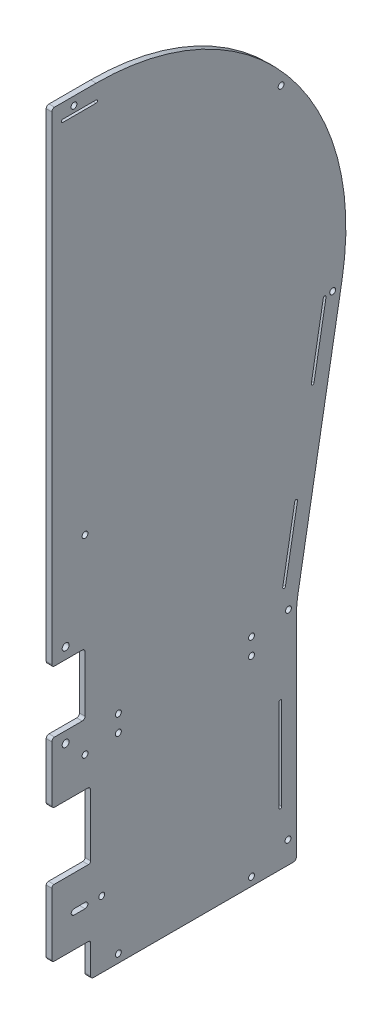
SolidWorks part; units mm, degrees
material "PC High Viscosity"
ref_plane "Front Plane" through (0, 0, 0) normal (0, 0, 1) x (1, 0, 0)
ref_plane "Top Plane" through (0, 0, 0) normal (0, 1, 0) x (1, 0, 0)
ref_plane "Right Plane" through (0, 0, 0) normal (1, 0, 0) x (0, 0, -1)
sketch "Sketch1" plane through (0, 0, 0) normal (1, 0, 0) x (0, 0, -1)
  line L0 (0, 0) -> (50.8, 0) construction
  line L1 (313.4482, -313.012) -> (263.1137, -598.4731) construction
  line L2 (260.7743, -625.2127) -> (260.7743, -865.7507) construction
  line L3 (0, 19.05) -> (50.8, 19.05)
  line L4 (332.2088, -316.32) -> (281.8743, -601.7811)
  line L5 (279.8243, -625.2127) -> (279.8243, -865.7507)
  line L6 (0, 19.05) -> (0, -534.7716)
  line L7 (0, -534.7716) -> (38.1, -534.7716)
  line L8 (38.1, -534.7716) -> (38.1, -605.1296)
  line L9 (38.1, -605.1296) -> (0, -605.1296)
  line L10 (0, -605.1296) -> (0, -674.7002)
  line L11 (0, -674.7002) -> (44.45, -674.7002)
  line L12 (44.45, -674.7002) -> (44.45, -865.7507)
  line L13 (44.45, -865.7507) -> (279.8243, -865.7507)
  line L14 (0, 1.5875) -> (50.8, 1.5875) construction
  line L15 (315.0116, -313.2876) -> (264.6771, -598.7487) construction
  line L16 (262.3618, -625.2127) -> (262.3618, -865.7507) construction
  arc A0 (50.8, 0) -> (313.4482, -313.012) centre (50.8, -266.7) cw construction
  arc A1 (263.1137, -598.4731) -> (260.7743, -625.2127) centre (414.7618, -625.2127) ccw construction
  arc A2 (50.8, 19.05) -> (332.2088, -316.32) centre (50.8, -266.7) cw
  arc A3 (281.8743, -601.7811) -> (279.8243, -625.2127) centre (414.7618, -625.2127) ccw
  arc A4 (50.8, 1.5875) -> (315.0116, -313.2876) centre (50.8, -266.7) cw construction
  arc A5 (264.6771, -598.7487) -> (262.3618, -625.2127) centre (414.7618, -625.2127) ccw construction
  point P23 (0, -333.375)
  point P25 (0, -3.175)
  point P27 (0, -681.0502)
  point P28 (0, -535.1526)
  dimension "D1" = 266.7
  dimension "D2" = 153.9875
  dimension "D3" = 80
  dimension "D4" = 50.8
  dimension "D5" = 240.538
  dimension "D6" = 289.8648
  dimension "D8" = 3.175
  dimension "D9" = 330.2
  dimension "D10" = 70.358
  dimension "D11" = 38.1
  dimension "D12" = 201.7776
  dimension "D13" = 0.381
  dimension "D14" = 347.6752
  dimension "D15" = 6.35
  dimension "D16" = 44.45
  dimension "D18" = 216.3243
  dimension "D7" = 19.05
  dimension "D17" = 1.5875
extrude "Boss-Extrude1" add sketch "Sketch1" along normal blind 6.35
hole_wizard "1/4 Clearance Hole1" positions "Sketch2" profile "Sketch3" hole size "1/4" standard "ANSI Inch" end condition through all
sketch "Sketch2" plane through (6.35, 0, 0) normal (1, 0, 0) x (0, 0, -1)
  line L0 (0, 1.5875) -> (50.8, 1.5875) construction
  line L1 (0, 19.05) -> (0, -534.7716) construction
  line L2 (256.3201, -94.2481) -> (262.4006, -89.146) construction
  line L6 (256.3201, -94.2481) -> (278.7716, -121.0047) construction
  line L8 (315.0116, -313.2876) -> (264.6771, -598.7487) construction
  line L9 (313.4482, -313.012) -> (315.0116, -313.2876) construction
  line L11 (262.9417, -611.9302) -> (270.849, -612.622) construction
  line L13 (262.9417, -611.9302) -> (264.7529, -591.2286) construction
  line L15 (262.3618, -625.2127) -> (262.3618, -865.7507) construction
  line L16 (44.45, -865.7507) -> (279.8243, -865.7507) construction
  line L17 (0, -605.1296) -> (0, -674.7002) construction
  line L18 (38.1, -569.9506) -> (0, -569.9506) construction
  line L19 (38.1, -534.7716) -> (38.1, -605.1296) construction
  line L23 (0, 19.05) -> (0, -534.7716) construction
  line L25 (44.45, -674.7002) -> (44.45, -865.7507) construction
  line L26 (44.45, -865.7507) -> (279.8243, -865.7507) construction
  line L27 (44.45, -627.9051) -> (279.8243, -627.9051) construction
  line L28 (279.8243, -865.7507) -> (279.8243, -625.2127) construction
  arc A0 (315.0116, -313.2876) -> (50.8, 1.5875) centre (50.8, -266.7) ccw construction
  arc A1 (264.6771, -598.7487) -> (262.3618, -625.2127) centre (414.7618, -625.2127) ccw construction
  point P0 (25.4, 9.525)
  point P2 (262.4006, -89.146)
  point P4 (321.4502, -322.4829)
  point P6 (270.849, -612.622)
  point P8 (270.2993, -840.3507)
  point P10 (38.1, -639.9149)
  point P12 (38.1, -422.275)
  point P68 (0, -639.9149)
  point P97 (76.2, -637.4301)
  point P99 (228.6, -637.4301)
  point P101 (76.2, -856.2257)
  point P103 (228.6, -856.2257)
  point P122 (228.6, -618.3801)
  point P123 (76.2, -618.3801)
  point P126 (57.15, -789.5507)
  point P127 (186.2677, -856.2257)
  dimension "D1" = 7.9375
  dimension "D2" = 25.4
  dimension "D3" = 7.9375
  dimension "D4" = 7.9375
  dimension "D5" = 7.9375
  dimension "D6" = 7.9375
  dimension "D7" = 7.9375
  dimension "D8" = 25.4
  dimension "D9" = 38.1
  dimension "D10" = 38.1
  dimension "D11" = 88.9
  dimension "D12" = 76.2
  dimension "D13" = 12.7
  dimension "D14" = 152.4
  dimension "D15" = 31.75
  dimension "D16" = 9.525
  dimension "D17" = 237.8456
  dimension "D18" = 9.525
sketch "Sketch3" plane through (6.35, 9.525, -25.4) normal (0, 1, 0) x (0, 0, -1)
  line L0 (0, 0) -> (0, 6.35)
  line L1 (0, 6.35) -> (3.3782, 6.35)
  line L2 (3.3782, 6.35) -> (3.3782, 0)
  line L5 (3.3782, 0) -> (0, 0)
  line L11 (0, -6.35) -> (0, 107.95) construction
  dimension "Thru Hole Dia." = 6.7564
  dimension "Thru Hole Depth" = 6.35
sketch "Sketch4" plane through (6.35, 0, 0) normal (1, 0, 0) x (0, 0, -1)
  line L0 (50.8, 0.7937) -> (12.7, 0.7937) construction
  line L1 (50.8, -0.7937) -> (12.7, -0.7938)
  line L2 (50.8, 2.3812) -> (12.7, 2.3812)
  line L3 (50.8, 0) -> (50.8, 1.5875) construction
  line L4 (312.3003, -324.0935) -> (298.5169, -402.2626) construction
  line L5 (313.8636, -324.3691) -> (300.0803, -402.5383)
  line L6 (310.7369, -323.8178) -> (296.9535, -401.9869)
  line L7 (313.4482, -313.012) -> (263.1137, -598.4731) construction
  line L8 (311.5186, -323.9556) -> (313.0819, -324.2313) construction
  line L9 (315.0116, -313.2876) -> (264.6771, -598.7487) construction
  line L10 (289.8444, -456.0182) -> (288.281, -455.7425) construction
  line L11 (265.8251, -587.6672) -> (279.6084, -509.4981) construction
  line L12 (267.3885, -587.9429) -> (281.1718, -509.7738)
  line L13 (264.2617, -587.3916) -> (278.045, -509.2224)
  line L14 (261.5681, -803.8382) -> (261.5681, -699.0632) construction
  line L15 (259.9806, -803.8382) -> (259.9806, -699.0632)
  line L16 (263.1556, -803.8382) -> (263.1556, -699.0632)
  line L17 (44.45, -865.7507) -> (279.8243, -865.7507) construction
  line L18 (260.7743, -803.8382) -> (262.3618, -803.8382) construction
  line L19 (260.7743, -625.2127) -> (260.7743, -865.7507) construction
  line L20 (262.3618, -625.2127) -> (262.3618, -865.7507) construction
  arc A0 (50.8, -0.7937) -> (50.8, 2.3812) centre (50.8, 0.7937) ccw
  arc A1 (12.7, 2.3812) -> (12.7, -0.7938) centre (12.7, 0.7937) ccw
  arc A2 (313.8636, -324.3691) -> (310.7369, -323.8178) centre (312.3003, -324.0935) ccw
  arc A3 (296.9535, -401.9869) -> (300.0803, -402.5383) centre (298.5169, -402.2626) ccw
  arc A4 (267.3885, -587.9429) -> (264.2617, -587.3916) centre (265.8251, -587.6672) cw
  arc A5 (278.045, -509.2224) -> (281.1718, -509.7738) centre (279.6084, -509.4981) cw
  arc A6 (259.9806, -803.8382) -> (263.1556, -803.8382) centre (261.5681, -803.8382) ccw
  arc A7 (263.1556, -699.0632) -> (259.9806, -699.0632) centre (261.5681, -699.0632) ccw
  point P2 (31.75, 0.7937)
  point P13 (305.4086, -363.178)
  point P29 (272.7168, -548.5827)
  point P36 (261.5681, -751.4507)
  dimension "D1" = 3.175
  dimension "D2" = 41.275
  dimension "D3" = 3.175
  dimension "D4" = 79.375
  dimension "D5" = 11.1125
  dimension "D6" = 3.175
  dimension "D7" = 104.775
  dimension "D8" = 61.9125
extrude "Cut-Extrude1" cut sketch "Sketch4" against normal through all
fillet "Fillet1" radius 3.175 9 edges at (3.175, 19.05, 0) (3.175, -865.7507, -279.8243) (3.175, -865.7507, -44.45) (3.175, -674.7002, -44.45) (3.175, -674.7002, 0) (3.175, -605.1296, 0) (3.175, -605.1296, -38.1) (3.175, -534.7716, 0) (3.175, -534.7716, -38.1)
sketch "Sketch5" plane through (6.35, 0, 0) normal (1, 0, 0) x (0, 0, -1)
  line L0 (44.45, -677.8752) -> (44.45, -862.5757) construction
  line L1 (44.45, -750.9002) -> (0, -750.9002)
  line L2 (44.45, -750.9002) -> (44.45, -827.1002)
  line L3 (44.45, -827.1002) -> (0, -827.1002)
  line L4 (0, -750.9002) -> (0, -827.1002)
  line L6 (3.175, -674.7002) -> (41.275, -674.7002) construction
  line L7 (0, -608.3046) -> (0, -671.5252) construction
  dimension "D1" = 76.2
  dimension "D2" = 76.2
extrude "Boss-Extrude2" add sketch "Sketch5" against normal up to surface (6.35 mm away) up to face at (0, 0.7937, -31.75)
fillet "Fillet2" radius 2.54 4 edges at (3.175, -750.9002, -44.45) (3.175, -750.9002, 0) (3.175, -827.1002, 0) (3.175, -827.1002, -44.45)
hole_wizard "1/4 (0.25) Diameter Slot1" positions "Sketch8" profile "Sketch9" size "1/4" standard "ANSI Inch" slot yes end condition through all
sketch "Sketch8" plane through (6.35, 0, 0) normal (1, 0, 0) x (0, 0, -1)
  line L0 (41.275, -789.5507) -> (22.225, -789.5507) construction
  line L1 (44.45, -677.8752) -> (44.45, -748.3602) construction
  circle A3 centre (57.15, -789.5507) radius 3.3782 construction
  circle A4 centre (57.15, -789.5507) radius 3.3782 construction
  point P0 (31.75, -789.5507)
  dimension "D1" = 19.05
  dimension "D2" = 3.175
sketch "Sketch9" plane through (6.35, -789.5507, -31.75) normal (0, 1, 0) x (0, 0, -1)
  line L0 (0, 0) -> (0, 6.35)
  line L1 (0, 6.35) -> (3.175, 6.35)
  line L2 (3.175, 6.35) -> (3.175, 0)
  line L5 (3.175, 0) -> (0, 0)
  line L11 (0, -6.35) -> (0, 107.95) construction
  dimension "Thru Hole Dia." = 6.35
  dimension "Thru Hole Depth" = 6.35
hole_wizard "5/16 (0.3125) Diameter Hole1" positions "Sketch10" profile "Sketch11" hole size "5/16" standard "ANSI Inch" end condition through all
sketch "Sketch10" plane through (6.35, 0, 0) normal (1, 0, 0) x (0, 0, -1)
  line L0 (38.1, -569.9506) -> (0, -569.9506) construction
  line L1 (38.1, -537.9466) -> (38.1, -601.9546) construction
  line L3 (0, 15.875) -> (0, -531.5966) construction
  line L4 (3.175, -534.7716) -> (34.925, -534.7716) construction
  point P0 (15.875, -522.0716)
  point P11 (15.875, -617.8296)
  dimension "D1" = 12.7
  dimension "D2" = 15.875
sketch "Sketch11" plane through (6.35, -522.0716, -15.875) normal (0, 1, 0) x (0, 0, -1)
  line L0 (0, 0) -> (0, 6.35)
  line L1 (0, 6.35) -> (3.9687, 6.35)
  line L2 (3.9687, 6.35) -> (3.9687, 0)
  line L5 (3.9687, 0) -> (0, 0)
  line L11 (0, -6.35) -> (0, 107.95) construction
  dimension "Thru Hole Dia." = 7.9375
  dimension "Thru Hole Depth" = 6.35
